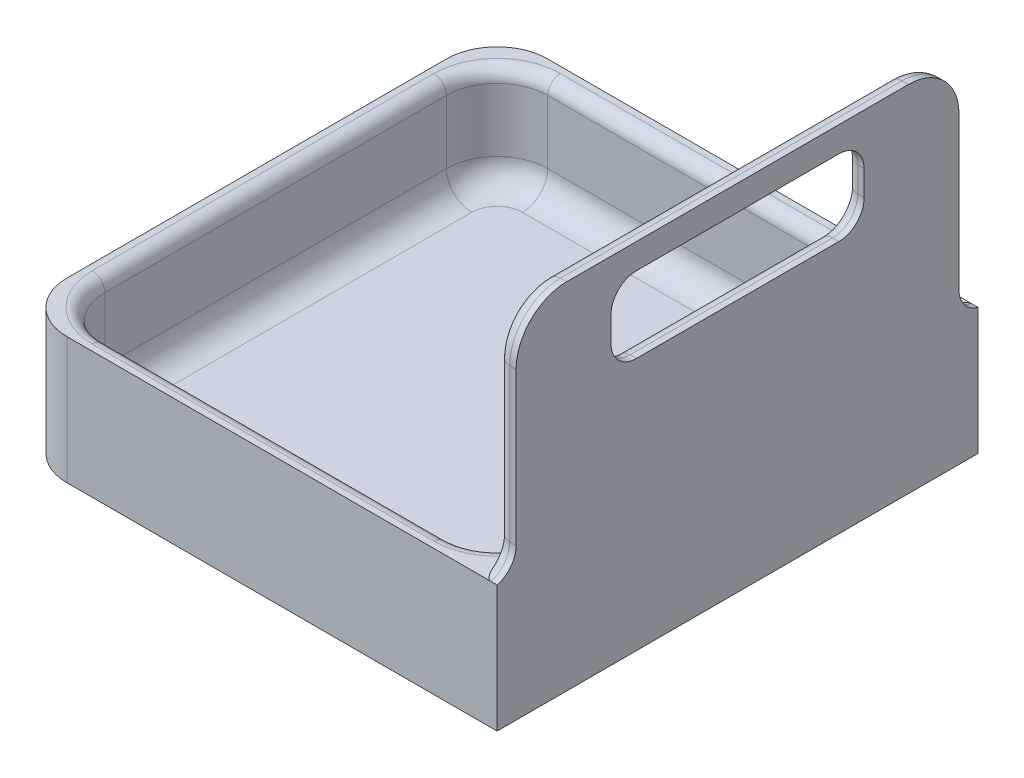
SolidWorks part; units mm, degrees
ref_plane "Front Plane" through (0, 0, 0) normal (0, 0, 1) x (1, 0, 0)
ref_plane "Top Plane" through (0, 0, 0) normal (0, 1, 0) x (1, 0, 0)
ref_plane "Right Plane" through (0, 0, 0) normal (1, 0, 0) x (0, 0, -1)
sketch "Sketch1" plane through (0, 0, 0) normal (0, 1, 0) x (1, 0, 0)
  line L1 (-95, -95) -> (95, -95)
  line L2 (-95, -95) -> (-95, 95)
  line L3 (-95, 95) -> (95, 95)
  line L4 (95, -95) -> (95, 95)
  line L5 (-95, -95) -> (95, 95) construction
  line L6 (-95, 95) -> (95, -95) construction
  point P0 (0, 0)
  dimension "D1" = 190
  dimension "D2" = 190
extrude "Boss-Extrude1" add sketch "Sketch1" along normal blind 10
sketch "Sketch2" plane through (0, 10, 0) normal (0, 1, 0) x (1, 0, 0)
  line L0 (-95, -95) -> (95, -95) construction
  line L1 (-95, 95) -> (-95, -95) construction
  line L2 (95, -95) -> (95, 95) construction
  line L3 (95, 95) -> (-95, 95) construction
  line L4 (-95, -95) -> (95, -95)
  line L5 (-95, 95) -> (-95, -95)
  line L6 (95, -95) -> (95, 95)
  line L7 (95, 95) -> (-95, 95)
  line L9 (-87.5, -87.5) -> (87.5, -87.5)
  line L10 (-87.5, -87.5) -> (-87.5, 87.5)
  line L11 (-87.5, 87.5) -> (87.5, 87.5)
  line L12 (87.5, -87.5) -> (87.5, 87.5)
  line L13 (-87.5, -87.5) -> (87.5, 87.5) construction
  line L14 (-87.5, 87.5) -> (87.5, -87.5) construction
  point P3 (0, 0)
  dimension "D1" = 175
  dimension "D2" = 175
extrude "Boss-Extrude2" add sketch "Sketch2" along normal blind 40
sketch "Sketch3" plane through (0, 50, 0) normal (0, 1, 0) x (1, 0, 0)
  line L0 (87.5, 87.5) -> (95, 87.5)
  line L1 (95, -95) -> (95, 95) construction
  line L2 (87.5, -87.5) -> (87.5, 87.5) construction
  line L3 (95, -87.5) -> (95, 87.5)
  line L4 (87.5, -87.5) -> (87.5, 87.5)
  line L5 (87.5, -87.5) -> (95, -87.5)
extrude "Boss-Extrude3" add sketch "Sketch3" along normal blind 90
sketch "Sketch4" plane through (87.5, 0, 0) normal (-1, 0, 0) x (0, 0, 1)
  line L0 (-87.5, 140) -> (87.5, 140) construction
  line L1 (-50, 100) -> (50, 100)
  line L2 (-50, 100) -> (-50, 130)
  line L3 (-50, 130) -> (50, 130)
  line L4 (50, 100) -> (50, 130)
  line L5 (-50, 100) -> (50, 130) construction
  line L6 (-50, 130) -> (50, 100) construction
  point P0 (0, 115)
  dimension "D1" = 100
  dimension "D2" = 30
  dimension "D3" = 10
extrude "Cut-Extrude1" cut sketch "Sketch4" against normal through all
fillet "Fillet2" radius 20 8 edges at (91.25, 140, -87.5) (91.25, 140, 87.5) (87.5, 30, 87.5) (87.5, 30, -87.5) (-87.5, 30, 87.5) (-87.5, 30, -87.5) (-95, 25, -95) (-95, 25, 95)
fillet "Fillet3" radius 10 14 edges at (81.6421, 10, 81.6421) (0, 10, 87.5) (-81.6421, 10, 81.6421) (-87.5, 10, 0) (-81.6421, 10, -81.6421) (0, 10, -87.5) (81.6421, 10, -81.6421) (87.5, 10, 0) (91.25, 50, -87.5) (91.25, 50, 87.5) (91.25, 130, 50) (91.25, 100, 50) (91.25, 130, -50) (91.25, 100, -50)
fillet "Fillet4" radius 5 22 edges at (81.6421, 50, -81.6421) (0, 50, -87.5) (-81.6421, 50, -81.6421) (-87.5, 50, 0) (-81.6421, 50, 81.6421) (81.6421, 50, 81.6421) (87.5, 102.9289, -47.0711) (87.5, 115, -50) (87.5, 127.0711, -47.0711) (87.5, 130, 0) (87.5, 127.0711, 47.0711) (87.5, 115, 50) (87.5, 102.9289, 47.0711) (0, 50, 87.5) (87.5, 100, 0) (87.5, 53.5587, -89.5943) (87.5, 89.8412, -87.5) (87.5, 134.1421, -81.6421) (87.5, 53.5587, 89.5943) (87.5, 89.8412, 87.5) (87.5, 134.1421, 81.6421) (87.5, 140, 0)
sketch "Sketch5" plane through (87.5, 0, 0) normal (-1, 0, 0) x (0, 0, 1)
  line L0 (67.5, 10) -> (-67.5, 10) construction
  line L1 (-11.5, 10) -> (11.5, 10)
  line L2 (-11.5, 10) -> (-11.5, 73)
  line L3 (-11.5, 73) -> (11.5, 73)
  line L4 (11.5, 10) -> (11.5, 73)
  line L5 (-11.5, 10) -> (11.5, 73) construction
  line L6 (-11.5, 73) -> (11.5, 10) construction
  point P0 (0, 41.5)
  point P7 (0, 10)
  dimension "D1" = 63
  dimension "D2" = 23
extrude "Cut-Extrude2" cut sketch "Sketch5" against normal blind 2 and the other way blind 90
